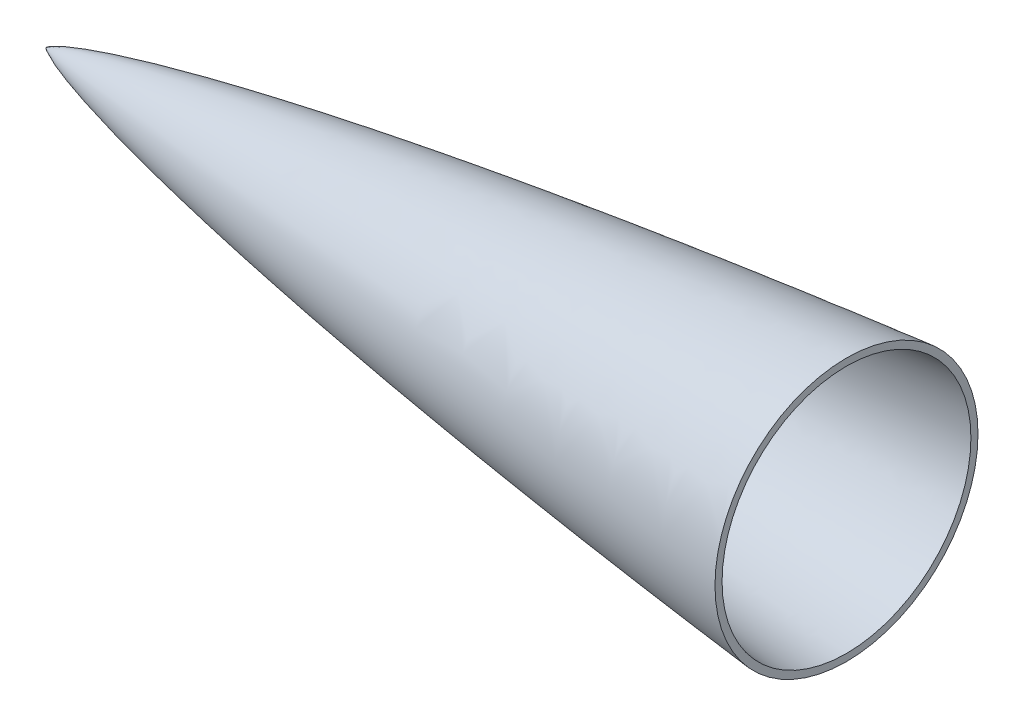
SolidWorks part; units mm, degrees
ref_plane "Front Plane" through (0, 0, 0) normal (0, 0, 1) x (1, 0, 0)
ref_plane "Top Plane" through (0, 0, 0) normal (0, 1, 0) x (1, 0, 0)
ref_plane "Right Plane" through (0, 0, 0) normal (1, 0, 0) x (0, 0, -1)
sketch "Sketch2" plane through (0, 0, 0) normal (0, 1, 0) x (1, 0, 0)
  line L0 (0, 0) -> (186.2, 0)
  line L1 (186.2, 0) -> (186.2, 30.5942)
  spline S0 degree 4 poles (0, 0) (0.0031, 0.0089) (0.0111, 0.0257) (0.0338, 0.0559) (0.0701, 0.0952) (0.1142, 0.1363) (0.1781, 0.1898) (0.2651, 0.2559) (0.3949, 0.3452) (0.607, 0.4767) (0.9521, 0.6686) (1.5402, 0.9598) (2.5741, 1.4116) (4.4139, 2.1149) (7.6024, 3.1739) (13.1065, 4.7592) (21.4404, 6.8338) (32.2223, 9.1851) (44.8484, 11.6455) (58.226, 14.0196) (69.9564, 15.9447) (80.0264, 17.506) (90.1038, 19.0036) (100.194, 20.4428) (110.2852, 21.8148) (120.3976, 23.1287) (128.8107, 24.1849) (134.7327, 24.9088) (139.7534, 25.5109) (144.8775, 26.1134) (149.8111, 26.687) (155.9483, 27.3807) (162.3431, 28.0928) (169.6409, 28.8782) (175.5202, 29.5034) (183.0749, 30.2794) (187.498, 30.7264) (193.3679, 31.3094) (197.7185, 31.7328) (201.3952, 32.0865) (203.6241, 32.2976) (204.8291, 32.4117) knots 0 0 0 0 0 0.00018 0.00036 0.00072 0.00103 0.001339 0.001964 0.002822 0.00406 0.00614 0.00956 0.015447 0.025766 0.044032 0.074197 0.125648 0.19101 0.256372 0.321734 0.387096 0.419777 0.452458 0.51782 0.583183 0.615864 0.648545 0.681226 0.697566 0.713907 0.746588 0.779269 0.81195 0.844631 0.877312 0.909993 0.932495 0.954996 0.977498 1 1 1 1 1 construction
  spline S1 degree 4 poles (0, 0) (0.0031, 0.0089) (0.0111, 0.0257) (0.0338, 0.0559) (0.0701, 0.0952) (0.1142, 0.1363) (0.1781, 0.1898) (0.2651, 0.2559) (0.3949, 0.3452) (0.607, 0.4767) (0.9521, 0.6686) (1.5402, 0.9598) (2.5741, 1.4116) (4.4139, 2.1149) (7.6024, 3.1739) (13.1065, 4.7592) (21.4404, 6.8338) (32.2223, 9.1851) (44.8484, 11.6455) (58.226, 14.0196) (69.9564, 15.9447) (80.0264, 17.506) (90.1038, 19.0036) (100.194, 20.4428) (110.2852, 21.8148) (120.3976, 23.1287) (128.8107, 24.1849) (134.7327, 24.9088) (139.7534, 25.5109) (144.8775, 26.1134) (149.8111, 26.687) (155.9483, 27.3807) (162.3431, 28.0928) (169.6409, 28.8782) (175.5202, 29.5034) (181.6647, 30.1346) (184.6624, 30.4393) (186.2, 30.5942) knots 0 0 0 0 0 0.00018 0.00036 0.00072 0.00103 0.001339 0.001964 0.002822 0.00406 0.00614 0.00956 0.015447 0.025766 0.044032 0.074197 0.125648 0.19101 0.256372 0.321734 0.387096 0.419777 0.452458 0.51782 0.583183 0.615864 0.648545 0.681226 0.697566 0.713907 0.746588 0.779269 0.81195 0.844631 0.877312 0.909993 0.909993 0.909993 0.909993 0.909993
revolve "Revolve1" add sketch "Sketch2" angle 360 about L0
shell "Shell1" thickness 1.64 removed face at (186.2, 0, 30.5942)
